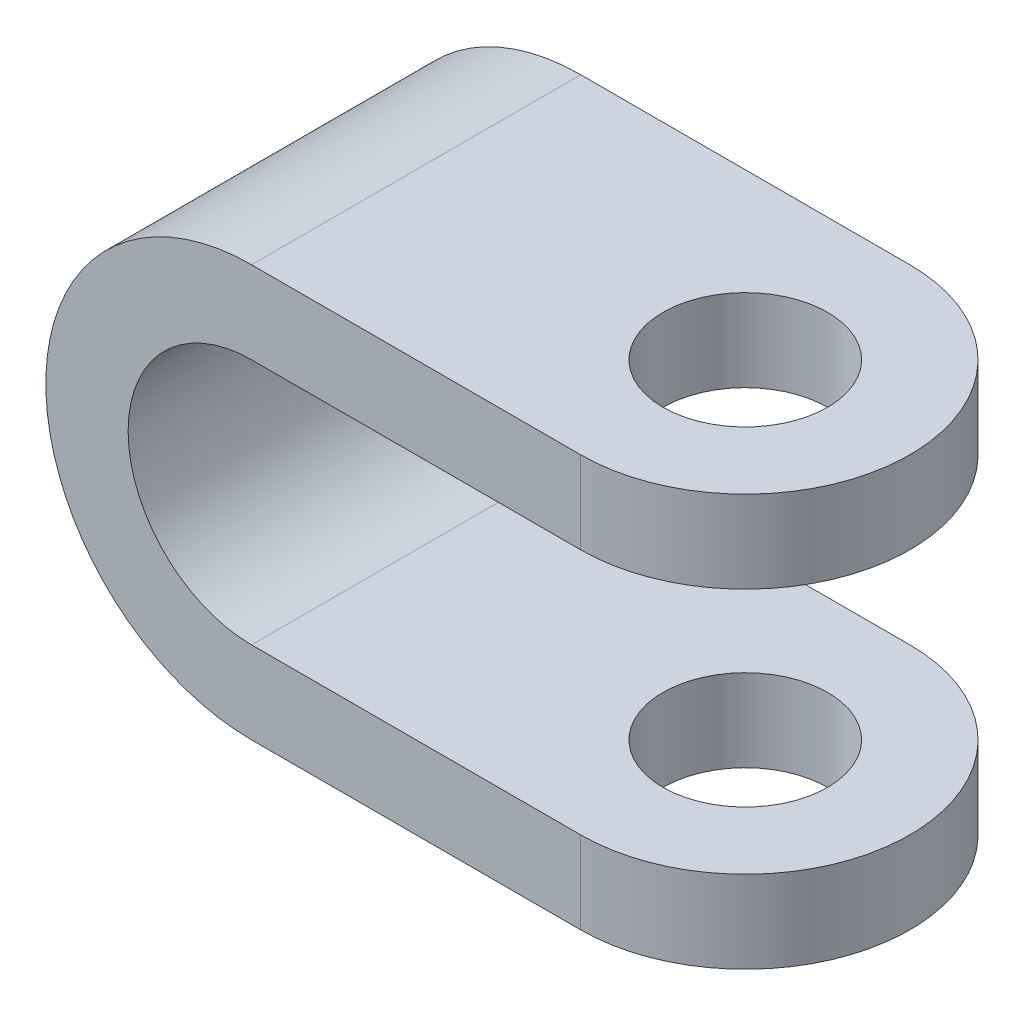
SolidWorks part; units mm, degrees
ref_plane "Front" through (0, 0, 0) normal (0, 0, 1) x (1, 0, 0)
ref_plane "Top" through (0, 0, 0) normal (0, 1, 0) x (1, 0, 0)
ref_plane "Right" through (0, 0, 0) normal (1, 0, 0) x (0, 0, -1)
sketch "Sketch1" plane through (0, 0, 0) normal (0, 0, 1) x (1, 0, 0)
  line L0 (0, -15) -> (-60, -15)
  line L1 (-60, -65) -> (0, -65)
  arc A0 (-60, -15) -> (-60, -65) centre (-60, -40) ccw
  dimension "D3" = 25
  dimension "D1" = 15
  dimension "D2" = 60
extrude "Extrude-Thin1" add sketch "Sketch1" along normal blind 90 thin thin type one direction reverse wall 10
sketch "Sketch2" plane through (0, 0, 0) normal (0, 1, 0) x (1, 0, 0)
  line L0 (-85, -25) -> (-85, -65)
  line L1 (-85, 0) -> (-85, -90) construction
  line L2 (-85, -65) -> (-20, -65)
  line L3 (-20, -25) -> (-85, -25)
  line L4 (0, -90) -> (0, 0) construction
  arc A0 (-20, -65) -> (-20, -25) centre (-20, -45) ccw
  circle A1 centre (-20, -45) radius 10
  dimension "D2" = 25
  dimension "D3" = 20
  dimension "D1" = 40
extrude "Boss-Extrude1" add sketch "Sketch2" against normal blind 90 separate body
combine bodies "Combine1" operation type common bodies to combine 102 101
